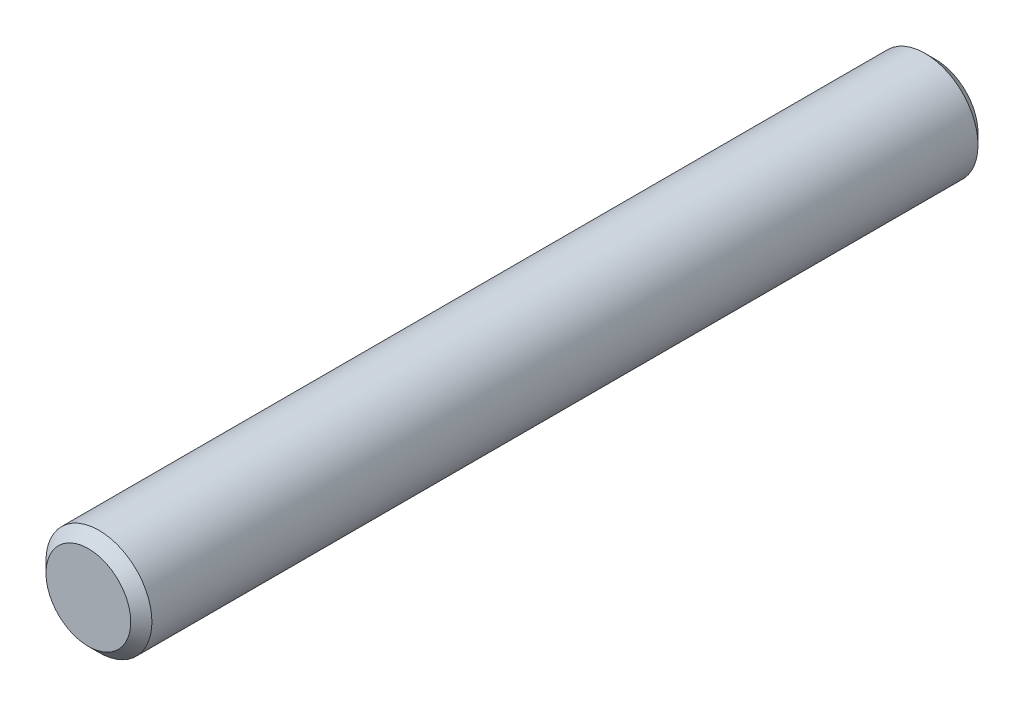
SolidWorks part; units mm, degrees
ref_plane "Front" through (0, 0, 0) normal (0, 0, 1) x (1, 0, 0)
ref_plane "Top" through (0, 0, 0) normal (0, 1, 0) x (1, 0, 0)
ref_plane "Right" through (0, 0, 0) normal (1, 0, 0) x (0, 0, -1)
sketch "Skizze1" plane through (0, 0, 0) normal (0, 0, 1) x (1, 0, 0)
  circle A0 centre (0, 0) radius 2.5
  dimension "D1" = 5
extrude "Aufsatz-Linear austragen1" add sketch "Skizze1" along normal blind 40
chamfer "Fase1" distance 0.5 angle 45 2 edges at (2.5, 0, 0) (2.5, 0, 40)
ref_axis "Axis1" through (0, 0, 39.5) along (0, 0, -1)
